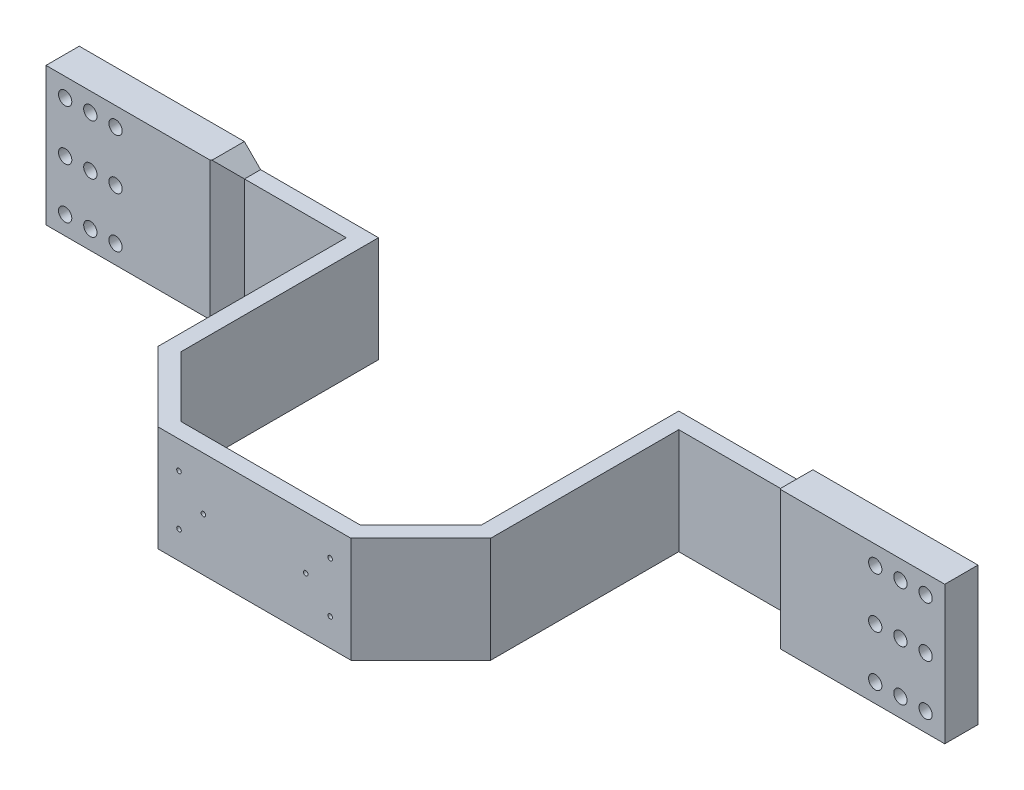
SolidWorks part; units mm, degrees
ref_plane "Front Plane" through (0, 0, 0) normal (0, 0, 1) x (1, 0, 0)
ref_plane "Top Plane" through (0, 0, 0) normal (0, 1, 0) x (1, 0, 0)
ref_plane "Right Plane" through (0, 0, 0) normal (1, 0, 0) x (0, 0, -1)
sketch "Sketch1" plane through (0, 0, 0) normal (0, 1, 0) x (1, 0, 0)
  line L0 (215, 0) -> (-215, 0)
  line L1 (-215, 0) -> (-215, -10)
  line L2 (215, 0) -> (215, -10)
  line L3 (74.5, 0) -> (-74.5, 0)
  line L4 (-74.5, 0) -> (-74.5, -120)
  line L5 (-74.5, -120) -> (74.5, -120)
  line L6 (74.5, -120) -> (74.5, 0)
  line L7 (223, 8) -> (223, -10)
  line L8 (223, 8) -> (-223, 8)
  line L9 (-223, 8) -> (-223, -10)
  line L10 (-82.5, 8) -> (-82.5, -128)
  line L11 (-82.5, -128) -> (82.5, -128)
  line L12 (82.5, -128) -> (82.5, 8)
  line L13 (82.5, 8) -> (-82.5, 8)
  line L14 (-223, -10) -> (-215, -10)
  line L15 (215, -10) -> (223, -10)
  line L16 (-74.5, 0) -> (-74.5, 8)
  line L17 (74.5, 0) -> (74.5, 8)
  line L18 (-74.5, -90) -> (-44.5, -120)
  line L19 (0, 0) -> (0, -120)
  line L20 (-82.5, -93.3137) -> (-47.8137, -128)
  line L21 (82.5, -93.3137) -> (47.8137, -128)
  line L22 (74.5, -90) -> (44.5, -120)
  line L23 (-215, 0) -> (-223, 0)
  line L24 (215, 0) -> (223, 0)
  point P4 (0, 0)
  point P10 (0, 0)
  dimension "D1" = 430
  dimension "D2" = 10
  dimension "D3" = 10
  dimension "D4" = 149
  dimension "D5" = 120
  dimension "D8" = 45
  dimension "D9" = 30
  dimension "D10" = 8
  dimension "D6" = 8
  dimension "D7" = 8
extrude "Boss-Extrude1" add sketch "Sketch1" along normal blind 52.45 contours L21 L5 L20 L11 | L4 L20 L5 L18 | L6 L22 L5 L21 | L21 L12 L0 L6 | L17 L0 L12 L8 | L2 L15 L7 L8 L12 L0 | L0 L16 L13 L10 | L10 L20 L4 L0 | L9 L14 L1 L0 L10 L8 region at (78.5, 0, -4) region at (78.4452, 0, 48.6843) region at (152.75, 0, -4) region at (62.1093, 0, 107.6093) region at (-78.4452, 0, 48.6843) region at (-78.5, 0, -4) region at (0, 0, 123.8971) region at (-152.75, 0, -4) region at (-62.1093, 0, 107.6093)
sketch "Sketch2" plane through (0, 0, 120) normal (0, 0, -1) x (-1, 0, 0)
  line L0 (0, 0) -> (0, 52.45)
  line L1 (44.5, 52.45) -> (-44.5, 52.45) construction
  line L2 (37.5, 26.225) -> (-37.5, 26.225)
  line L3 (-37.5, 13.725) -> (-37.5, 38.725)
  line L4 (37.5, 13.725) -> (37.5, 38.725)
  line L5 (25.4, 26.225) -> (-25.4, 26.225)
  point P8 (0, 26.225)
  point P11 (-37.5, 26.225)
  point P14 (37.5, 26.225)
  point P17 (0, 26.225)
  dimension "D1" = 75
  dimension "D2" = 25
  dimension "D3" = 25
  dimension "D4" = 50.8
hole_wizard "#4-40 Tapped Hole1" positions "Sketch5" profile "Sketch6" tap size "#4-40" standard "ANSI Inch" end condition through all
sketch "Sketch5" plane through (0, 0, 120) normal (0, 0, -1) x (-1, 0, 0)
  point P0 (-37.5, 38.725)
  point P3 (-37.5, 13.725)
  point P6 (37.5, 13.725)
  point P9 (37.5, 38.725)
  point P12 (-25.4, 26.225)
  point P15 (25.4, 26.225)
sketch "Sketch6" plane through (37.5, 38.725, 120) normal (1, 0, 0) x (0, 1, 0)
  line L0 (0, 0) -> (0, 8)
  line L1 (0, 8) -> (1.1303, 8)
  line L2 (1.1303, 8) -> (1.1303, 0)
  line L5 (1.1303, 0) -> (0, 0)
  line L11 (0, -6.35) -> (0, 107.95) construction
  dimension "Thru Tap Drill Dia." = 2.2606
  dimension "Thru Tap Drill Depth" = 8
cosmetic thread "Hole Thread1" parameters "D2"=2.8448
cosmetic thread "Hole Thread2" parameters "D2"=2.8448
cosmetic thread "Hole Thread3" parameters "D2"=2.8448
cosmetic thread "Hole Thread4" parameters "D2"=2.8448
cosmetic thread "Hole Thread5" parameters "D2"=2.8448
cosmetic thread "Hole Thread6" parameters "D2"=2.8448
sketch "Sketch12" plane through (0, 0, 120) normal (0, 0, -1) x (-1, 0, 0)
  line L0 (37.5, 26.225) -> (-37.5, 26.225) construction
  line L1 (25, 1.225) -> (-25, 1.225)
  line L2 (25, 1.225) -> (25, 51.225)
  line L3 (25, 51.225) -> (-25, 51.225)
  line L4 (-25, 1.225) -> (-25, 51.225)
  line L5 (25, 1.225) -> (-25, 51.225) construction
  line L6 (25, 51.225) -> (-25, 1.225) construction
  point P0 (0, 26.225)
  dimension "D1" = 50
  dimension "D2" = 50
sketch "Sketch13" plane through (0, 0, -8) normal (0, 0, -1) x (-1, 0, 0)
  line L0 (201, 26.225) -> (-201, 26.225)
  line L2 (-201, 1.225) -> (-201, 51.225)
  line L3 (201, 1.225) -> (201, 51.225)
  line L4 (-188.5, 1.225) -> (-188.5, 51.225)
  line L5 (-213.5, 1.225) -> (-213.5, 51.225)
  line L6 (0, 7.0406) -> (0, 45.4094)
  line L8 (0, 0) -> (0, 52.45) construction
  line L9 (213.5, 1.225) -> (213.5, 51.225)
  line L10 (188.5, 1.225) -> (188.5, 51.225)
  point P3 (0, 26.225)
  point P7 (-201, 26.225)
  point P10 (201, 26.225)
  point P13 (-188.5, 26.225)
  point P16 (-213.5, 26.225)
  point P19 (0, 26.225)
  dimension "D1" = 402
  dimension "D2" = 50
  dimension "D3" = 50
  dimension "D4" = 50
  dimension "D5" = 50
  dimension "D6" = 12.5
  dimension "D7" = 12.5
  dimension "D8" = 12.5
sketch "Sketch14" plane through (0, 0, -8) normal (0, 0, -1) x (-1, 0, 0)
  line L0 (0, -11.8283) -> (0, 64.2783)
  line L1 (-223, 0) -> (-143, 0)
  line L2 (-223, 0) -> (-223, -8.065)
  line L3 (-223, -8.065) -> (-143, -8.065)
  line L4 (-143, 0) -> (-143, -8.065)
  line L5 (-223, 52.45) -> (-143, 52.45)
  line L6 (-223, 52.45) -> (-223, 60.515)
  line L7 (-223, 60.515) -> (-143, 60.515)
  line L8 (-143, 52.45) -> (-143, 60.515)
  line L10 (223, -8.065) -> (143, -8.065)
  line L11 (143, 0) -> (143, -8.065)
  line L12 (223, 0) -> (143, 0)
  line L13 (223, 0) -> (223, -8.065)
  line L14 (223, 60.515) -> (143, 60.515)
  line L15 (143, 52.45) -> (143, 60.515)
  line L16 (223, 52.45) -> (143, 52.45)
  line L17 (223, 52.45) -> (223, 60.515)
  point P14 (0, 26.225)
  point P24 (-143, -4.0325)
  line M10 (74.5, 0) -> (223, 0)
  line M12 (223, 52.45) -> (74.5, 52.45)
  dimension "D1" = 8.065
  dimension "D2" = 8.065
  dimension "D3" = 80
  dimension "D4" = 80
extrude "Boss-Extrude2" add sketch "Sketch14" against normal up to surface (8 mm away) contours L5 L8 L7 L6 | L4 L1 L2 L3 | L13 L11 L10 M10 | L17 L14 L15 M12 region at (183, -4.0325, -8) region at (183, 56.4825, -8) region at (-183, -4.0325, -8) region at (-183, 56.4825, -8) up to face at (152.75, 26.225, 0)
sketch "Sketch19" plane through (0, 0, 0) normal (0, 0, 1) x (1, 0, 0)
  line L1 (-143, -8.065) -> (-223, -8.065)
  line L2 (-143, -8.065) -> (-143, 60.515)
  line L3 (-143, 60.515) -> (-223, 60.515)
  line L4 (-223, -8.065) -> (-223, 60.515)
  line L5 (143, -8.065) -> (223, -8.065)
  line L6 (143, -8.065) -> (143, 60.515)
  line L7 (143, 60.515) -> (223, 60.515)
  line L8 (223, -8.065) -> (223, 60.515)
extrude "Boss-Extrude3" add sketch "Sketch19" along normal blind 8.5
hole_wizard "CBORE for M6 SHCS2" positions "Sketch17" profile "Sketch18" counterbore size "M6" standard "ANSI Metric" end condition through all
sketch "Sketch17" plane through (0, 0, -8) normal (0, 0, -1) x (-1, 0, 0)
  line L0 (-213.5, 1.225) -> (-213.5, 51.225) construction
  line L1 (-188.5, 1.225) -> (-188.5, 51.225) construction
  line L2 (188.5, 1.225) -> (188.5, 51.225) construction
  line L3 (213.5, 1.225) -> (213.5, 51.225) construction
  point P0 (-201, 1.225)
  point P3 (-201, 26.225)
  point P6 (-201, 51.225)
  point P9 (201, 1.225)
  point P12 (201, 26.225)
  point P15 (201, 51.225)
  point P19 (-188.5, 51.225)
  point P22 (-213.5, 51.225)
  point P25 (-213.5, 1.225)
  point P28 (-213.5, 26.225)
  point P32 (-188.5, 26.225)
  point P36 (-188.5, 1.225)
  point P39 (188.5, 1.225)
  point P42 (188.5, 26.225)
  point P46 (188.5, 51.225)
  point P49 (213.5, 51.225)
  point P52 (213.5, 1.225)
  point P56 (213.5, 26.225)
sketch "Sketch18" plane through (201, 1.225, -8) normal (1, 0, 0) x (0, 1, 0)
  line L0 (0, 0) -> (0, 136)
  line L1 (0, 136) -> (3.3, 136)
  line L3 (3.3, 136) -> (3.3, 6)
  line L4 (3.3, 6) -> (5.5, 6)
  line L5 (5.5, 6) -> (5.5, 0)
  line L7 (5.5, 0) -> (0, 0)
  line L11 (0, -6.35) -> (0, 107.95) construction
  dimension "Thru Hole Dia." = 6.6
  dimension "Thru Hole Depth" = 136
  dimension "C'Bore Dia." = 11
  dimension "C'Bore Depth" = 6
chamfer "Chamfer1" distance 10 angle 45 4 edges at (143, 0, -4) (-143, 0, -4) (-143, 52.45, -4) (143, 52.45, -4)
chamfer "Chamfer2" distance 10 angle 45 1 edges at (143, 26.225, 0)
chamfer "Chamfer3" distance 10 angle 45 1 edges at (-143, 26.225, 0)
